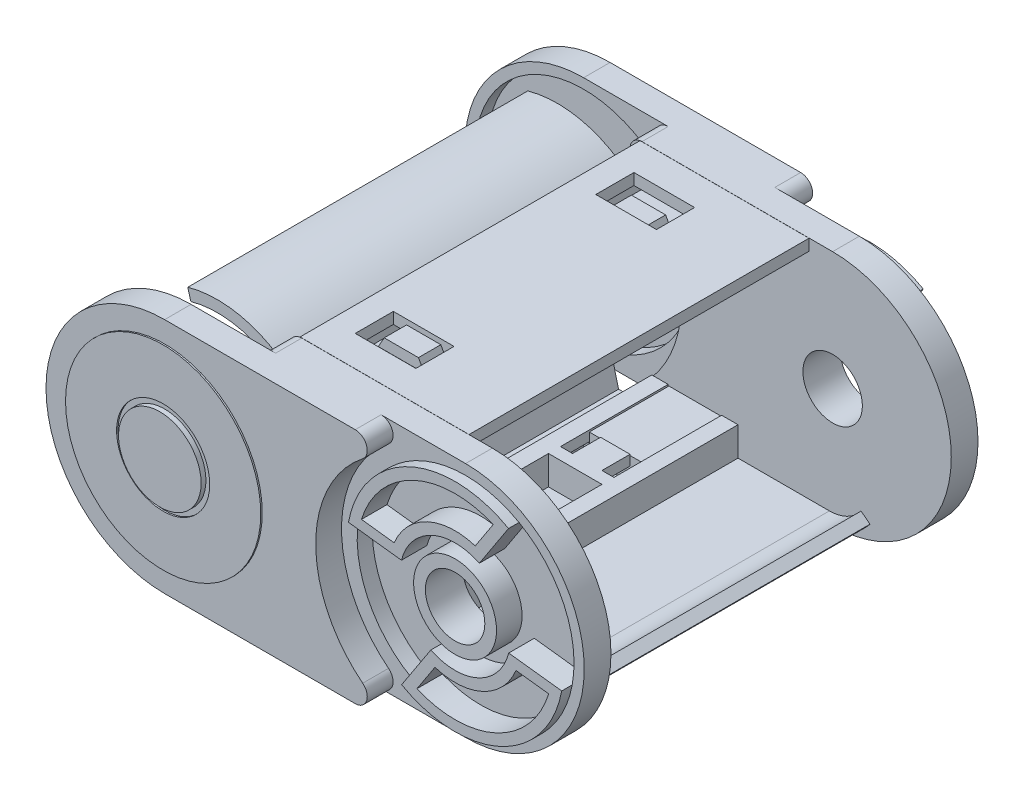
SolidWorks part; units mm, degrees
material "ABS"
ref_plane "Front Plane" through (0, 0, 0) normal (0, 0, 1) x (1, 0, 0)
ref_plane "Top Plane" through (0, 0, 0) normal (0, 1, 0) x (1, 0, 0)
ref_plane "Right Plane" through (0, 0, 0) normal (1, 0, 0) x (0, 0, -1)
sketch "Sketch1" plane through (0, 0, 0) normal (0, 0, 1) x (1, 0, 0)
  line L0 (0, 19.75) -> (45.8, 19.75)
  line L2 (45.8, -19.75) -> (0, -19.75)
  line L3 (0, 0) -> (45.8, 0) construction
  line L4 (22.9, 0) -> (22.9, 19.75) construction
  arc A0 (0, 19.75) -> (0, -19.75) centre (0, 0) ccw
  arc A1 (45.8, 19.75) -> (45.8, -19.75) centre (45.8, 0) cw
  point P1 (-19.75, 0)
  point P12 (65.55, 0)
  dimension "D1" = 39.5
  dimension "D2" = 85.3
  dimension "D3" = 45.8
extrude "Boss-Extrude1" add sketch "Sketch1" against normal blind 8.75 from offset 37.075
sketch "Sketch3" plane through (0, 0, 37.075) normal (0, 0, 1) x (1, 0, 0)
  line L6 (65.55, 0) -> (25.15, 0) construction
  circle A2 centre (45.8, 0) radius 20.65
  circle A3 centre (0, 0) radius 16.25
  arc A4 (45.8, -19.75) -> (45.8, 19.75) centre (45.8, 0) ccw construction
  circle A5 centre (0, 0) radius 7.75
  circle A6 centre (0, 0) radius 5.15
  point P4 (65.55, 0)
  dimension "D1" = 40.4
  dimension "D2" = 10.3
  dimension "D3" = 15.5
  dimension "D4" = 32.5
extrude "Cut-Extrude2" cut sketch "Sketch3" against normal blind 4.3 contours A2
extrude "Cut-Extrude10" cut sketch "Sketch3<3>" against normal through all contours A6 region at (0, 0, 37.075)
sketch "Sketch3<3>" plane through (0, 0, 37.075) normal (0, 0, 1) x (1, 0, 0) same geometry as "Sketch3"
extrude "Boss-Extrude11" add sketch "Sketch3<4>" along normal blind 0.25 contours A3 A5 region at (-15.7904, 0, 37.075)
sketch "Sketch3<4>" plane through (0, 0, 37.075) normal (0, 0, 1) x (1, 0, 0) same geometry as "Sketch3"
sketch "Sketch8" plane through (0, 0, 28.325) normal (0, 0, -1) x (-1, 0, 0)
  line L0 (19.75, 0) -> (-20.65, 0) construction
  circle A0 centre (0, 0) radius 20.65
  arc A1 (0, -19.75) -> (0, 19.75) centre (0, 0) ccw construction
  point P3 (-20.65, 0)
  point P4 (19.75, 0)
  dimension "D1" = 40.4
extrude "Cut-Extrude6" cut sketch "Sketch8" against normal blind 4.35
sketch "Sketch9" plane through (0, 0, 32.675) normal (0, 0, -1) x (-1, 0, 0)
  circle A0 centre (0, 0) radius 18.1
  dimension "D1" = 36.2
extrude "Cut-Extrude7" cut sketch "Sketch9" against normal blind 6.5 from surface starting at face at (34.5075, 0, 28.325)
sketch "Sketch10" plane through (0, 0, 34.825) normal (0, 0, -1) x (-1, 0, 0)
  line L0 (0, 0) -> (16.75, 0) construction
  line L1 (8.5625, 2.5) -> (16.75, 3.2)
  line L2 (16.75, 3.2) -> (16.75, -3.2)
  line L3 (16.75, -3.2) -> (8.5625, -2.5)
  line L4 (8.8724, 0.9207) -> (15.15, 1.4574)
  line L5 (15.15, 1.4574) -> (15.15, -1.4574)
  line L6 (15.15, -1.4574) -> (8.8724, -0.9207)
  line L7 (8.6988, 0.9058) -> (15.15, 1.4574) construction
  line L8 (15.15, -1.4574) -> (8.6988, -0.9058) construction
  line L9 (0, 0) -> (0, -8.92) construction
  line L10 (-8.8724, 0.9207) -> (-15.15, 1.4574)
  line L11 (-15.15, 1.4574) -> (-15.15, -1.4574)
  line L12 (-15.15, -1.4574) -> (-8.8724, -0.9207)
  line L13 (-16.75, -3.2) -> (-8.5625, -2.5)
  line L14 (-16.75, 3.2) -> (-16.75, -3.2)
  line L15 (-8.5625, 2.5) -> (-16.75, 3.2)
  circle A0 centre (0, 0) radius 7
  arc A1 (-8.8724, 0.9207) -> (-8.8724, -0.9207) centre (0, 0) ccw
  arc A2 (-8.5625, -2.5) -> (8.5625, -2.5) centre (0, 0) ccw
  arc A3 (8.5625, 2.5) -> (-8.5625, 2.5) centre (0, 0) ccw
  arc A4 (8.8724, -0.9207) -> (8.8724, 0.9207) centre (0, 0) ccw
  point P7 (16.75, 0)
  dimension "D1" = 14
  dimension "D2" = 17.84
  dimension "D3" = 5
  dimension "D4" = 6.4
  dimension "D5" = 16.75
  dimension "D6" = 1.6
extrude "Boss-Extrude3" add sketch "Sketch10" along normal blind 3.9
fillet "Fillet1" radius 0.5 4 edges at (-16.75, -3.2, 32.875) (-16.75, 3.2, 32.875) (16.75, -3.2, 32.875) (16.75, 3.2, 32.875)
sketch "Sketch11" plane through (0, 0, 30.925) normal (0, 0, -1) x (-1, 0, 0)
  circle A0 centre (0, 0) radius 7 construction
  circle A1 centre (0, 0) radius 7
extrude "Cut-Extrude8" cut sketch "Sketch11" against normal blind 4.6
fillet "Fillet2" radius 2 4 edges at (6.0299, 19.75, 30.5) (6.0299, -19.75, 30.5) (39.7701, -19.75, 34.925) (39.7701, 19.75, 34.925)
sketch "Sketch20" plane through (0, 0, 32.775) normal (0, 0, 1) x (1, 0, 0)
  circle A1 centre (45.8, 0) radius 18.05
  circle A2 centre (45.8, 0) radius 4.95
  dimension "D1" = 36.1
  dimension "D2" = 9.9
extrude "Cut-Extrude11" cut sketch "Sketch20" against normal through all contours A2 region at (45.8, 0, 32.775)
extrude "Cut-Extrude12" cut sketch "Sketch20<3>" against normal offset from surface (2.5 mm away) 6.8 contours A1 up to face at (16.25, 0, 37.075)
sketch "Sketch20<3>" plane through (0, 0, 32.775) normal (0, 0, 1) x (1, 0, 0) same geometry as "Sketch20"
sketch "Sketch21" plane through (0, 0, 30.275) normal (0, 0, 1) x (1, 0, 0)
  line L0 (54.6961, 15.7055) -> (49.8334, 8.2687)
  line L1 (45.8, 0) -> (38.1717, 16.3589) construction
  line L2 (28.0506, 3.2805) -> (36.8732, 2.2253)
  line L3 (45.8, 0) -> (63.6996, 8.3467) construction
  line L4 (45.8, 0) -> (0, 0) construction
  line L5 (52.1515, 15.0116) -> (49.152, 10.4243)
  line L6 (30.2178, 4.7838) -> (35.6599, 4.1329)
  line L7 (36.9039, -15.7055) -> (41.7666, -8.2687)
  line L8 (39.4485, -15.0116) -> (42.448, -10.4243)
  line L9 (61.3822, -4.7838) -> (55.9401, -4.1329)
  line L10 (63.5494, -3.2805) -> (54.7268, -2.2253)
  circle A0 centre (45.8, 0) radius 4.95 construction
  circle A1 centre (45.8, 0) radius 4.95
  circle A2 centre (45.8, 0) radius 6.9
  arc A3 (49.8334, 8.2687) -> (36.8732, 2.2253) centre (45.8, 0) ccw
  circle A4 centre (45.8, 0) radius 18.05 construction
  arc A5 (54.6961, 15.7055) -> (28.0506, 3.2805) centre (45.8, 0) ccw
  arc A6 (45.8, -19.75) -> (45.8, 19.75) centre (45.8, 0) ccw construction
  arc A7 (0, 19.75) -> (0, -19.75) centre (0, 0) ccw construction
  arc A8 (49.152, 10.4243) -> (35.6599, 4.1329) centre (45.8, 0) ccw
  arc A9 (52.1515, 15.0116) -> (30.2178, 4.7838) centre (45.8, 0) ccw
  arc A10 (54.7268, -2.2253) -> (41.7666, -8.2687) centre (45.8, 0) cw
  arc A11 (55.9401, -4.1329) -> (42.448, -10.4243) centre (45.8, 0) cw
  arc A12 (61.3822, -4.7838) -> (39.4485, -15.0116) centre (45.8, 0) cw
  arc A13 (63.5494, -3.2805) -> (36.9039, -15.7055) centre (45.8, 0) cw
  point P19 (-19.75, 0)
  dimension "D1" = 13.8
  dimension "D2" = 29.4
  dimension "D4" = 18.4
  dimension "D3" = 14.3
  dimension "D5" = 25
  dimension "D6" = 1.75
extrude "Boss-Extrude12" add sketch "Sketch21" along normal blind 4.25
sketch "Sketch12" plane through (0, 0, 28.325) normal (0, 0, -1) x (-1, 0, 0)
  line L0 (-27.45, 17.15) -> (-18.35, 17.15)
  line L1 (-22.9, 17.15) -> (-22.9, 13.25) construction
  line L2 (-27.45, 17.15) -> (-28.275, 15.65)
  line L3 (-28.275, 14.85) -> (-27.25, 14.85)
  line L4 (-27.25, 14.85) -> (-27.25, 13.25)
  line L5 (-18.55, 14.85) -> (-18.55, 13.25)
  line L6 (-17.525, 14.85) -> (-18.55, 14.85)
  line L7 (-18.35, 17.15) -> (-17.525, 15.65)
  line L8 (-18.55, 13.25) -> (-27.25, 13.25)
  line L9 (-28.275, 15.65) -> (-28.275, 14.85)
  line L10 (0, 0) -> (-45.8, 0) construction
  line L20 (-17.525, 15.65) -> (-17.525, 14.85)
  line L21 (-22.9, -17.15) -> (-22.9, -13.25) construction
  line L22 (-17.525, -15.65) -> (-17.525, -14.85)
  line L23 (-28.275, -15.65) -> (-28.275, -14.85)
  line L24 (-18.55, -13.25) -> (-27.25, -13.25)
  line L25 (-18.35, -17.15) -> (-17.525, -15.65)
  line L26 (-17.525, -14.85) -> (-18.55, -14.85)
  line L27 (-18.55, -14.85) -> (-18.55, -13.25)
  line L28 (-27.25, -14.85) -> (-27.25, -13.25)
  line L29 (-28.275, -14.85) -> (-27.25, -14.85)
  line L30 (-27.45, -17.15) -> (-28.275, -15.65)
  line L31 (-27.45, -17.15) -> (-18.35, -17.15)
  point P3 (-22.9, 17.15)
  point P17 (-22.9, 0)
  dimension "D1" = 10.75
  dimension "D3" = 26.5
  dimension "D4" = 34.3
  dimension "D5" = 8.7
  dimension "D6" = 2.3
  dimension "D7" = 0.8
  dimension "D8" = 9.1
extrude "Boss-Extrude4" add sketch "Sketch12" along normal offset from surface (13.25 mm away) 22 up to face at (16.25, 0, 37.075)
sketch "Sketch13" plane through (0, 0, 15.075) normal (0, 0, -1) x (-1, 0, 0)
  line L0 (-26.725, 17.15) -> (-25.75, 18.9)
  line L1 (-18.35, 17.15) -> (-27.45, 17.15) construction
  line L2 (-25.75, 18.9) -> (-20.05, 18.9)
  line L3 (-20.05, 18.9) -> (-19.075, 17.15)
  line L4 (-26.725, 17.15) -> (-19.075, 17.15)
  line L5 (-22.9, 18.9) -> (-22.9, 17.15) construction
  line L6 (0, 0) -> (-45.8, 0) construction
  line L8 (-20.05, -18.9) -> (-19.075, -17.15)
  line L9 (-26.725, -17.15) -> (-19.075, -17.15)
  line L10 (-26.725, -17.15) -> (-25.75, -18.9)
  line L11 (-25.75, -18.9) -> (-20.05, -18.9)
  point P8 (-22.9, 17.15)
  dimension "D1" = 7.65
  dimension "D2" = 5.7
  dimension "D3" = 1.75
extrude "Boss-Extrude5" add sketch "Sketch13" against normal blind 4.4 from offset 1.1 offset against normal yes
sketch "Sketch14" plane through (0, 0, 0) normal (0, 0, 1) x (1, 0, 0)
  line L0 (45.2873, 19.75) -> (8.74, 19.75)
  line L1 (45.8, 19.75) -> (14.0698, 19.75) construction
  line L2 (8.74, 19.75) -> (7.2253, 13.8823)
  line L3 (52.05, 16.3994) -> (50.5543, 15.2605)
  line L4 (45.2873, 17.87) -> (30.075, 17.87)
  line L5 (10.1963, 17.87) -> (8.4, 10.9111)
  line L6 (-10.34, 11.7476) -> (-9.0979, 10.3364)
  line L8 (30.075, 13.05) -> (30.075, 17.87)
  line L9 (27.35, 13.05) -> (30.075, 13.05)
  line L10 (27.35, 13.05) -> (27.35, 14.75)
  line L11 (27.35, 14.75) -> (28.375, 14.75)
  line L12 (28.375, 14.75) -> (28.375, 17.87)
  line L13 (28.375, 17.87) -> (17.425, 17.87)
  line L14 (41.15, 17.87) -> (10.1963, 17.87) construction
  line L15 (18.45, 13.05) -> (15.725, 13.05)
  line L16 (15.725, 13.05) -> (15.725, 17.87)
  line L17 (22.9, 13.25) -> (22.9, 19.75) construction
  line L18 (18.45, 13.25) -> (18.45, 14.75)
  line L19 (17.425, 14.75) -> (17.425, 15.65)
  line L20 (18.45, 14.75) -> (17.425, 14.75)
  line L21 (18.45, 13.05) -> (18.45, 14.75)
  line L22 (17.425, 14.75) -> (17.425, 17.87)
  line L23 (18.45, 14.75) -> (17.425, 14.75)
  line L24 (18.55, 13.25) -> (27.25, 13.25) construction
  line L25 (15.725, 17.87) -> (10.1963, 17.87)
  line L26 (52.05, 16.3994) -> (52.8335, 18.4552) construction
  line L27 (41.15, 19.75) -> (8.74, 19.75) construction
  arc A0 (7.2253, 13.8823) -> (-10.34, 11.7476) centre (0, 0) ccw
  arc A1 (8.4, 10.9111) -> (-9.0979, 10.3364) centre (0, 0) ccw
  arc A3 (45.8, -19.75) -> (45.8, 19.75) centre (45.8, 0) ccw construction
  arc A4 (52.05, 16.3994) -> (45.2873, 19.75) centre (45.2873, 11.25) ccw
  arc A5 (50.5543, 15.2605) -> (45.2873, 17.87) centre (45.2873, 11.25) ccw
  point P28 (65.55, 0)
  point P30 (45.8, 0)
  point P37 (52.05, 16.3994)
  dimension "D1" = 15.65
  dimension "D5" = 2.2
  dimension "D10" = 17
  dimension "D2" = 14.16
  dimension "D3" = 33.24
  dimension "D4" = 14.5
  dimension "D7" = 0.1
  dimension "D9" = 13.5
  dimension "D6" = 1.88
  dimension "D8" = 1.7
extrude "Boss-Extrude6" add sketch "Sketch14" along normal mid plane 56.6 separate body
sketch "Sketch15" plane through (0, 19.75, 0) normal (0, 1, 0) x (1, 0, 0)
  line L1 (27.95, -16.85) -> (17.85, -16.85)
  line L2 (27.95, -16.85) -> (27.95, -23.2)
  line L5 (27.95, -23.2) -> (17.85, -23.2)
  line L6 (17.85, -16.85) -> (17.85, -23.2)
  line L7 (22.9, -23.2) -> (22.9, -16.85) construction
  line L8 (27.95, -20.025) -> (17.85, -20.025) construction
  line L9 (0, 0) -> (44.1536, 0) construction
  line L10 (17.85, 16.85) -> (17.85, 23.2)
  line L11 (27.95, 23.2) -> (17.85, 23.2)
  line L12 (27.95, 16.85) -> (27.95, 23.2)
  line L13 (27.95, 16.85) -> (17.85, 16.85)
  line L14 (19.075, -16.175) -> (26.725, -20.575) construction
  point P14 (22.9, -18.375)
  point P172 (22.9, -20.025)
  dimension "D1" = 10.1
  dimension "D2" = 33.7
  dimension "D3" = 46.4
extrude "Cut-Extrude9" cut sketch "Sketch15" against normal up to surface (5 mm away) up to face at (27.8625, 14.75, 0)
sketch "Sketch16" plane through (0, 13.05, 0) normal (0, -1, 0) x (1, 0, 0)
  line L0 (30.075, 28.3) -> (30.075, -28.3) construction
  line L1 (30.075, 10.375) -> (15.725, 10.375)
  line L2 (30.075, 10.375) -> (30.075, -10.375)
  line L3 (30.075, -10.375) -> (15.725, -10.375)
  line L4 (15.725, 10.375) -> (15.725, -10.375)
  line L5 (22.9, -10.375) -> (22.9, 10.375) construction
  line L6 (30.075, 0) -> (15.725, 0) construction
  line L7 (15.725, 28.3) -> (15.725, -28.3) construction
  line L8 (18.45, 28.3) -> (18.45, -28.3) construction
  line L9 (27.35, -8.375) -> (18.45, -8.375)
  line L10 (27.35, -8.375) -> (27.35, 8.375)
  line L11 (27.35, 8.375) -> (18.45, 8.375)
  line L12 (18.45, -8.375) -> (18.45, 8.375)
  line L13 (22.9, 8.375) -> (22.9, -8.375) construction
  line L14 (27.35, 0) -> (18.45, 0) construction
  point P10 (22.9, 0)
  point P212 (22.9, 0)
  dimension "D1" = 20.75
  dimension "D2" = 2
extrude "Boss-Extrude7" add sketch "Sketch16" against normal up to surface (4.82 mm away) up to face at (37.6812, 17.87, 0)
sketch "Sketch17" plane through (0, 13.05, 0) normal (0, -1, 0) x (1, 0, 0)
  line L0 (22.9, 10.375) -> (22.9, -10.375) construction
  line L1 (28.375, 10.375) -> (17.425, 10.375) construction
  line L2 (18.45, -10.375) -> (27.35, -10.375) construction
  line L3 (25.35, 10.375) -> (25.35, 15.05)
  line L4 (20.45, 10.375) -> (20.45, 15.05)
  line L5 (20.45, 15.05) -> (25.35, 15.05)
  line L6 (22.9, 0) -> (27.35, 0) construction
  line L8 (25.35, 10.375) -> (20.45, 10.375)
  line L9 (20.45, -10.375) -> (20.45, -15.05)
  line L10 (20.45, -15.05) -> (25.35, -15.05)
  line L11 (25.35, -10.375) -> (25.35, -15.05)
  line L12 (25.35, -10.375) -> (20.45, -10.375)
  line L13 (27.35, 8.375) -> (27.35, -8.375) construction
  dimension "D1" = 4.9
  dimension "D2" = 30.1
extrude "Boss-Extrude8" add sketch "Sketch17" against normal up to surface (1.7 mm away) up to face at (17.9375, 14.75, 19.3375)
sketch "Sketch18" plane through (0, 0, 37.075) normal (0, 0, 1) x (1, 0, 0)
  circle A0 centre (0, 0) radius 6.875
  dimension "D1" = 13.75
extrude "Boss-Extrude9" add sketch "Sketch18" along normal blind 0.8 separate body
sketch "Sketch19" plane through (0, 0, 37.075) normal (0, 0, -1) x (-1, 0, 0)
  circle A2 centre (0, 0) radius 5.1
  circle A4 centre (0, 0) radius 5.1
  dimension "D1" = 0.05
extrude "Boss-Extrude10" add sketch "Sketch19" along normal blind 8
mirror "Mirror1" about plane through (0, 0, 0) normal (0, 0, 1) of bodies 113 121
mirror "Mirror2" about plane through (0, 0, 0) normal (0, 1, 0) of bodies 119 115
sketch "Sketch22" plane through (0, -19.75, 0) normal (0, -1, 0) x (1, 0, 0)
  line L0 (45.8, 28.325) -> (65.55, 28.325) construction
  line L1 (54.05, 28.325) -> (41.9, 28.325)
  line L2 (54.05, 28.325) -> (54.05, -28.325)
  line L3 (54.05, -28.325) -> (41.9, -28.325)
  line L4 (41.9, 28.325) -> (41.9, -28.325)
  line L5 (47.975, -28.325) -> (47.975, 28.325) construction
  line L6 (54.05, 0) -> (41.9, 0) construction
  line L7 (14.0698, -28.325) -> (45.8, -28.325) construction
  line L8 (52.05, 28.3) -> (52.05, -28.3) construction
  line L9 (25.75, 20.575) -> (20.05, 20.575) construction
  point P14 (22.9, 20.575)
  point P268 (47.975, 0)
  dimension "D1" = 2
  dimension "D2" = 19
extrude "Cut-Extrude13" cut sketch "Sketch22" against normal through all
sketch "Sketch23" plane through (0, 0, 0) normal (0, 0, 1) x (1, 0, 0)
  line L0 (15.225, 17.87) -> (14.1999, 13.8987)
  line L1 (8.4, 10.9111) -> (10.1963, 17.87) construction
  line L2 (10.1963, 17.87) -> (15.725, 17.87) construction
  line L3 (15.225, 17.87) -> (15.225, 19.75)
  line L4 (41.9, 19.75) -> (8.74, 19.75) construction
  line L5 (15.225, 19.75) -> (13.7687, 19.75)
  line L6 (13.7687, 19.75) -> (12.3795, 14.3685)
  line L7 (10.1963, 17.87) -> (8.376, 18.3399) construction
  line L8 (8.74, 19.75) -> (7.2253, 13.8823) construction
  line L9 (14.7124, 15.8843) -> (12.8921, 16.3542) construction
  line L10 (-4.925, 17.5729) -> (-4.4177, 15.7627)
  line L11 (30.075, 13.05) -> (30.075, 17.87) construction
  arc A1 (10.3855, 12.6538) -> (-4.4177, 15.7627) centre (0, 0) ccw
  arc A3 (11.5782, 14.107) -> (-4.925, 17.5729) centre (0, 0) ccw
  arc A4 (12.3795, 14.3685) -> (11.5782, 14.107) centre (11.8954, 14.4935) cw
  arc A5 (14.1999, 13.8987) -> (10.3855, 12.6538) centre (11.8954, 14.4935) cw
  point P1 (-2.9817, 15.3633)
  point P8 (-6.625, 15.7151)
  point P28 (11.2249, 12.8028)
  point P29 (13.4228, 10.8883)
  point P30 (0, 0)
  point P32 (0, 0)
  point P35 (0, 0)
  point P36 (0, 0)
  point P37 (0, 0)
  point P38 (-6.625, 21.2666)
  dimension "D3" = 0.5
  dimension "D5" = 2.38
  dimension "D6" = 18.25
  dimension "D1" = 0.5
  dimension "D2" = 35
  dimension "D4" = 1.88
sketch "Sketch24" plane through (0, 0, 0) normal (0, 0, 1) x (1, 0, 0)
  line L1 (15.225, 19.75) -> (-22.9807, 19.75)
  line L2 (15.225, 19.75) -> (15.225, 7.5314)
  line L3 (15.225, 7.5314) -> (-22.9807, 7.5314)
  line L4 (-22.9807, 19.75) -> (-22.9807, 7.5314)
  line L5 (-3.8779, 7.5314) -> (-3.8779, 19.75) construction
  line L6 (15.225, 13.6407) -> (-22.9807, 13.6407) construction
  point P108 (-3.8779, 13.6407)
extrude "Cut-Extrude14" cut sketch "Sketch24" against normal through all both and the other way through all
extrude "Boss-Extrude13" add sketch "Sketch23" along normal up to surface (28.3 mm away) and the other way up to surface (28.3 mm away) up to face at (24.3156, 16.12, 28.3) other way up to face at (24.3156, 16.12, -28.3)
